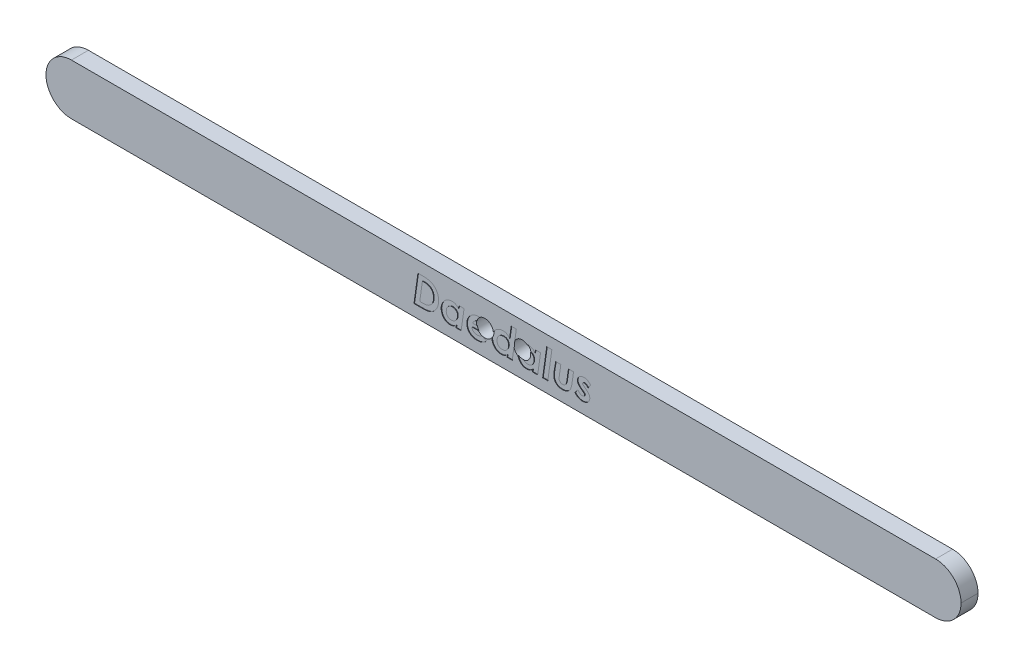
SolidWorks part; units mm, degrees
material "Acrylic (Medium-high impact)"
ref_plane "Front Plane" through (0, 0, 0) normal (0, 0, 1) x (1, 0, 0)
ref_plane "Top Plane" through (0, 0, 0) normal (0, 1, 0) x (1, 0, 0)
ref_plane "Right Plane" through (0, 0, 0) normal (1, 0, 0) x (0, 0, -1)
sketch "Sketch1" plane through (0, 0, 0) normal (0, 0, 1) x (1, 0, 0)
  line L0 (0, -1.65) -> (0, 1.65) construction
  line L1 (-80.9, 4.5) -> (80.9, 4.5)
  line L2 (-80.9, 4.5) -> (-80.9, -4.5)
  line L3 (-80.9, -4.5) -> (80.9, -4.5)
  line L4 (80.9, 4.5) -> (80.9, -4.5)
  circle A3 centre (-3.3, 0) radius 1.5
  circle A4 centre (3.3, 0) radius 1.5
  point P4 (0, 4.5)
  point P6 (-80.9, 0)
  point P13 (0, 0)
  point P14 (0, 0)
  dimension "D3" = 3
  dimension "D4" = 3.6
  dimension "D2" = 161.8
  dimension "D1" = 9
extrude "Boss-Extrude1" add sketch "Sketch1" along normal mid plane 3
fillet "Fillet1" radius 4.5 4 edges at (80.9, -4.5, 0) (80.9, 4.5, 0) (-80.9, -4.5, 0) (-80.9, 4.5, 0)
sketch "Sketch2" plane through (0, 0, 1.5) normal (0, 0, 1) x (1, 0, 0)
  line L0 (-31.1678, -2.5) -> (31.1678, -2.5) construction
  line L2 (-76.4, -4.5) -> (76.4, -4.5) construction
  text T0 "<b><i>Daedalus</i></b>" font "Century Gothic" height 5
  point P5 (0, 0)
  point P7 (0, -2.5)
  dimension "D1" = 2
extrude "Cut-Extrude1" cut sketch "Sketch2" against normal blind 0.1
